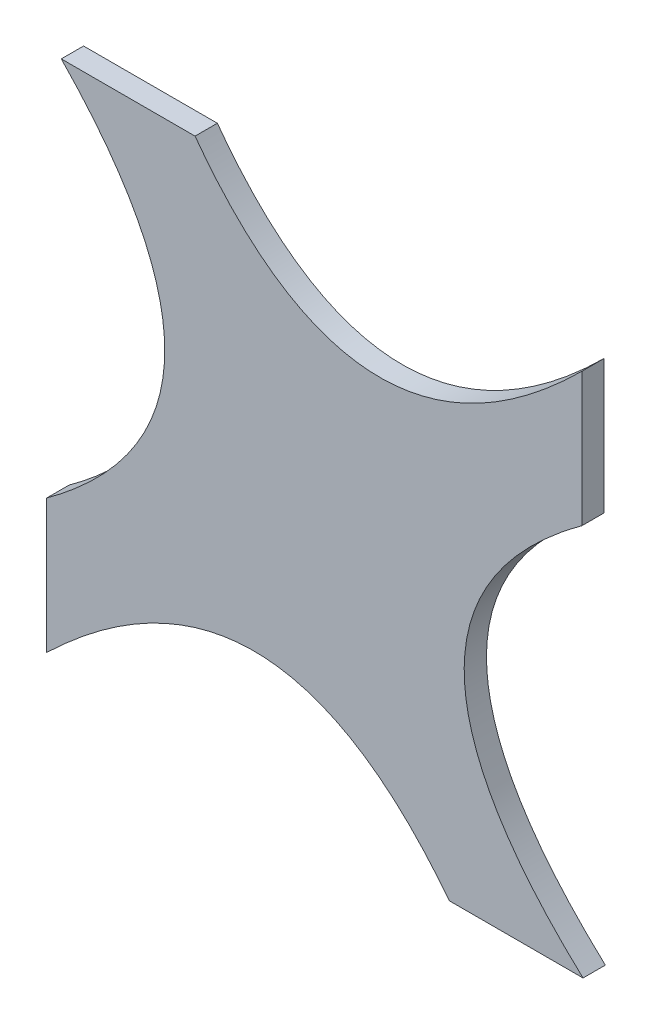
SolidWorks part; units mm, degrees
ref_plane "Front Plane" through (0, 0, 0) normal (0, 0, 1) x (1, 0, 0)
ref_plane "Top Plane" through (0, 0, 0) normal (0, 1, 0) x (1, 0, 0)
ref_plane "Right Plane" through (0, 0, 0) normal (1, 0, 0) x (0, 0, -1)
sketch "Sketch1" plane through (0, 0, 0) normal (0, 0, 1) x (1, 0, 0)
  line L0 (-17.0055, 52.5) -> (-47.0055, 52.5)
  line L1 (69.715, 50.1759) -> (69.715, 20.1759)
  line L2 (70.0032, -67.5) -> (40.0032, -67.5)
  line L3 (-50.285, -34.4245) -> (-50.285, -64.4245)
  line L9 (-32.0055, 52.5) -> (55.0032, -67.5) construction
  line L10 (-50.285, -49.4245) -> (69.715, 35.1759) construction
  circle A0 centre (9.715, -7.1243) radius 35 construction
  spline S0 degree 2 poles (69.715, 50.1759) (20.5363, 1.4069) (-17.0055, 52.5) knots 0 0 0 1 1 1
  spline S1 degree 2 poles (-47.0055, 52.5) (0.981, 3.0592) (-50.285, -34.4245) knots 0 0 0 1 1 1
  spline S2 degree 2 poles (-50.285, -64.4245) (0.2517, -15.8836) (40.0032, -67.5) knots 0 0 0 1 1 1
  spline S3 degree 2 poles (70.0032, -67.5) (16.8396, -18.5212) (69.715, 20.1759) knots 0 0 0 1 1 1
  dimension "D2" = 70
  dimension "D1" = 30
extrude "Boss-Extrude1" add sketch "Sketch1" along normal blind 5
